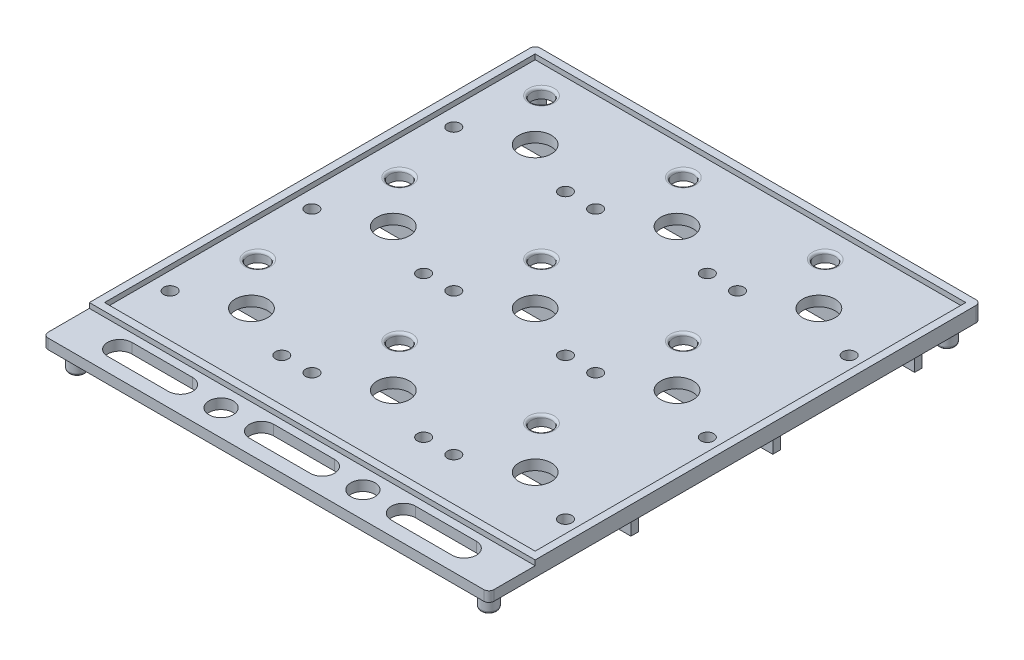
SolidWorks part; units mm, degrees
ref_plane "Front Plane" through (0, 0, 0) normal (0, 0, 1) x (1, 0, 0)
ref_plane "Top Plane" through (0, 0, 0) normal (0, 1, 0) x (1, 0, 0)
ref_plane "Right Plane" through (0, 0, 0) normal (1, 0, 0) x (0, 0, -1)
sketch "Sketch1" plane through (0, 0, 0) normal (0, 1, 0) x (1, 0, 0)
  line L1 (-25.4006, 105.41) -> (114.2994, 105.41)
  line L2 (-25.4006, 105.41) -> (-25.4006, -48.7985)
  line L3 (-25.4006, -48.7985) -> (114.2994, -48.7985)
  line L4 (114.2994, 105.41) -> (114.2994, -48.7985)
  circle A0 centre (44.45, 80.01) radius 5.08
  circle A1 centre (44.45, 80.01) radius 2.1
  circle A2 centre (61.95, 72.01) radius 2
  circle A3 centre (26.95, 72.01) radius 2
  circle A4 centre (0, 80.01) radius 5.08
  circle A5 centre (0, 80.01) radius 2.1
  circle A6 centre (17.5, 72.01) radius 2
  circle A7 centre (-17.5, 72.01) radius 2
  circle A8 centre (44.45, 35.56) radius 5.08
  circle A9 centre (44.45, 35.56) radius 2.1
  circle A10 centre (61.95, 27.56) radius 2
  circle A11 centre (26.95, 27.56) radius 2
  circle A12 centre (0, 35.56) radius 5.08
  circle A13 centre (0, 35.56) radius 2.1
  circle A14 centre (17.5, 27.56) radius 2
  circle A15 centre (-17.5, 27.56) radius 2
  circle A16 centre (44.45, -8.89) radius 5.08
  circle A17 centre (44.45, -8.89) radius 2.1
  circle A18 centre (61.95, -16.89) radius 2
  circle A19 centre (26.95, -16.89) radius 2
  circle A20 centre (0, -8.89) radius 5.08
  circle A21 centre (0, -8.89) radius 2.1
  circle A22 centre (17.5, -16.89) radius 2
  circle A23 centre (-17.5, -16.89) radius 2
  circle A24 centre (88.9, 80.01) radius 5.08
  circle A25 centre (88.9, 80.01) radius 2.1
  circle A26 centre (106.4, 72.01) radius 2
  circle A27 centre (71.4, 72.01) radius 2
  circle A28 centre (88.9, 35.56) radius 5.08
  circle A29 centre (88.9, 35.56) radius 2.1
  circle A30 centre (106.4, 27.56) radius 2
  circle A31 centre (71.4, 27.56) radius 2
  circle A32 centre (88.9, -8.89) radius 5.08
  circle A33 centre (88.9, -8.89) radius 2.1
  circle A34 centre (106.4, -16.89) radius 2
  circle A35 centre (71.4, -16.89) radius 2
  dimension "D3" = 7.8994
  dimension "D4" = 4
  dimension "D5" = 35
  dimension "D6" = 8
  dimension "D1" = 10.16
  dimension "D2" = 4
  dimension "D13" = 17.5
  dimension "D7" = 25.4
  dimension "D8" = 0
  dimension "D9" = 154.2085
  dimension "D10" = 139.7
  dimension "D11" = 3
  dimension "D12" = 3
extrude "Boss-Extrude4" add sketch "Sketch1" along normal blind 3.175 contours L4 L1 L2 L3 A27 A26 A24 region at (44.4494, 0, -28.0568)
sketch "Sketch4" plane through (0, 3.175, 0) normal (0, 1, 0) x (1, 0, 0)
  line L0 (-25.4006, 105.41) -> (-25.4006, -48.7985) construction
  line L1 (-25.4006, -31.9087) -> (114.2994, -31.9087)
  line L2 (-25.4006, -31.9087) -> (-25.4006, -34.29)
  line L3 (-25.4006, -34.29) -> (114.2994, -34.29)
  line L4 (114.2994, -31.9087) -> (114.2994, -34.29)
  line L5 (114.2994, 105.41) -> (114.2994, -48.7985) construction
  line L7 (-25.4006, -48.7985) -> (114.2994, -48.7985) construction
  dimension "D1" = 16.8897
  dimension "D2" = 14.5085
extrude "Boss-Extrude7" add sketch "Sketch4" along normal blind 1.5875
sketch "Sketch5" plane through (0, 3.175, 0) normal (0, -1, 0) x (1, 0, 0)
  line L0 (-25.4006, -105.41) -> (114.2994, -105.41) construction
  line L1 (-25.4006, -105.41) -> (-25.4006, 31.9087) construction
  circle A0 centre (-12.3037, -94.3) radius 3.175
  circle A1 centre (32.1463, -94.3) radius 3.175
  circle A2 centre (76.5963, -94.3) radius 3.175
  circle A3 centre (32.1463, -49.85) radius 3.175
  circle A4 centre (76.5963, -49.85) radius 3.175
  circle A5 centre (32.1463, -5.4) radius 3.175
  circle A6 centre (76.5963, -5.4) radius 3.175
  circle A7 centre (-12.3037, -49.85) radius 3.175
  circle A8 centre (-12.3037, -5.4) radius 3.175
  dimension "D1" = 11.11
  dimension "D2" = 13.0969
  dimension "D3" = 3
  dimension "D5" = 6.35
  dimension "D4" = 3
extrude "Cut-Extrude1" cut sketch "Sketch5" along normal up to next contours A0 | A1 | A2 | A4 | A3 | A7 | A8 | A5 | A6 region at (-12.3037, 3.175, -94.3) region at (32.1463, 3.175, -94.3) region at (76.5963, 3.175, -94.3) region at (32.1463, 3.175, -49.85) region at (76.5963, 3.175, -49.85) region at (32.1463, 3.175, -5.4) region at (76.5963, 3.175, -5.4) region at (-12.3037, 3.175, -49.85) region at (-12.3037, 3.175, -5.4)
sketch "Sketch7" plane through (0, 3.175, 0) normal (0, 1, 0) x (1, 0, 0)
  line L0 (9.525, -40.64) -> (-9.525, -40.64) construction
  line L1 (9.525, -44.4349) -> (-9.525, -44.4349)
  line L2 (9.525, -36.8451) -> (-9.525, -36.8451)
  line L3 (53.975, -40.64) -> (34.925, -40.64) construction
  line L4 (53.975, -44.4349) -> (34.925, -44.4349)
  line L5 (53.975, -36.8451) -> (34.925, -36.8451)
  line L6 (98.425, -40.64) -> (79.375, -40.64) construction
  line L7 (98.425, -44.4349) -> (79.375, -44.4349)
  line L8 (98.425, -36.8451) -> (79.375, -36.8451)
  line L9 (-25.4006, -34.29) -> (114.2994, -34.29) construction
  line L10 (-25.4006, -34.29) -> (114.2994, -34.29) construction
  arc A0 (9.525, -44.4349) -> (9.525, -36.8451) centre (9.525, -40.64) ccw
  arc A1 (-9.525, -36.8451) -> (-9.525, -44.4349) centre (-9.525, -40.64) ccw
  arc A2 (53.975, -44.4349) -> (53.975, -36.8451) centre (53.975, -40.64) ccw
  arc A3 (34.925, -36.8451) -> (34.925, -44.4349) centre (34.925, -40.64) ccw
  arc A4 (98.425, -44.4349) -> (98.425, -36.8451) centre (98.425, -40.64) ccw
  arc A5 (79.375, -36.8451) -> (79.375, -44.4349) centre (79.375, -40.64) ccw
  circle A6 centre (22.225, -40.64) radius 3.7949
  circle A8 centre (66.675, -40.64) radius 3.7949
  point P2 (0, -40.64)
  point P11 (44.45, -40.64)
  point P18 (88.9, -40.64)
  dimension "D4" = 12.7
  dimension "D1" = 0
  dimension "D2" = 19.05
  dimension "D6" = 12.7
  dimension "D8" = 6.35
  dimension "D10" = 6.35
  dimension "D11" = 6.35
  dimension "D3" = 3
extrude "Cut-Extrude2" cut sketch "Sketch7" against normal up to next
fillet "Fillet1" radius 0.7937 9 edges at (-12.3037, 3.175, -46.675) (32.1463, 3.175, -46.675) (76.5963, 3.175, -46.675) (76.5963, 3.175, -91.125) (32.1463, 3.175, -91.125) (-12.3037, 3.175, -91.125) (76.5963, 3.175, -2.225) (32.1463, 3.175, -2.225) (-12.3037, 3.175, -2.225)
sketch "Sketch8" plane through (0, 0, 0) normal (0, 1, 0) x (1, 0, 0)
  line L0 (-25.4006, 105.41) -> (-25.4006, -48.7985) construction
  line L1 (-25.4006, 0.6375) -> (114.2994, 0.6375)
  line L2 (-25.4006, 0.6375) -> (-25.4006, -1.7437)
  line L3 (-25.4006, -1.7437) -> (114.2994, -1.7437)
  line L4 (114.2994, 0.6375) -> (114.2994, -1.7437)
  line L5 (114.2994, 105.41) -> (114.2994, -31.9087) construction
  circle A0 centre (-12.3037, 5.4) radius 3.175 construction
  dimension "D1" = 4.7625
  dimension "D2" = 2.3813
extrude "Boss-Extrude8" add sketch "Sketch8" against normal blind 6.35
pattern_linear "LPattern2" count 3 spacing 44.45 along (0, 0, -1) of "Boss-Extrude8"
sketch "Sketch9" plane through (0, 0, 0) normal (0, -1, 0) x (1, 0, 0)
  line L1 (-25.4006, 48.7985) -> (114.2994, 48.7985)
  line L2 (-25.4006, 48.7985) -> (-25.4006, -105.41)
  line L3 (-25.4006, -105.41) -> (114.2994, -105.41)
  line L4 (114.2994, 48.7985) -> (114.2994, -105.41)
  line L5 (111.7594, -102.87) -> (-22.8606, -102.87)
  line L6 (111.7594, -102.87) -> (111.7594, 46.2585)
  line L7 (111.7594, 46.2585) -> (-22.8606, 46.2585)
  line L8 (-22.8606, -102.87) -> (-22.8606, 46.2585)
  dimension "D1" = 2.54
  dimension "D2" = 2.54
  dimension "D3" = 2.54
  dimension "D4" = 2.54
extrude "Cut-Extrude3" cut sketch "Sketch9" along normal blind 6.35
sketch "Sketch10" plane through (0, 3.175, 0) normal (0, 1, 0) x (1, 0, 0)
  line L0 (114.2994, -31.9087) -> (-25.4006, -31.9087) construction
  line L1 (-25.4006, -34.29) -> (114.2994, -34.29)
  line L2 (-25.4006, -34.29) -> (-25.4006, 105.41)
  line L3 (-25.4006, 105.41) -> (114.2994, 105.41)
  line L4 (114.2994, -34.29) -> (114.2994, 105.41)
  line L5 (111.9181, -31.9087) -> (-23.0194, -31.9087)
  line L6 (111.9181, -31.9087) -> (111.9181, 103.0288)
  line L7 (111.9181, 103.0288) -> (-23.0194, 103.0288)
  line L8 (-23.0194, -31.9087) -> (-23.0194, 103.0288)
  line L9 (-25.4006, 105.41) -> (-25.4006, -31.9087) construction
  dimension "D1" = 2.3813
  dimension "D2" = 2.3813
  dimension "D3" = 2.3813
  dimension "D4" = 2.3813
extrude "Boss-Extrude9" add sketch "Sketch10" along normal blind 1.5875
sketch "Sketch11" plane through (0, 0, 0) normal (0, -1, 0) x (1, 0, 0)
  line L0 (-25.4006, -105.41) -> (114.2994, -105.41) construction
  line L1 (-25.4006, -105.41) -> (-25.4006, 48.7985) construction
  line L2 (114.2994, -105.41) -> (114.2994, 48.7985) construction
  line L3 (-25.4006, 48.7985) -> (114.2994, 48.7985) construction
  circle A0 centre (-20.0666, 43.4645) radius 2.54
  circle A1 centre (108.9654, 43.4645) radius 2.54
  circle A2 centre (108.9654, -100.076) radius 2.54
  circle A3 centre (-20.0666, -100.076) radius 2.54
  dimension "D2" = 5.08
  dimension "D3" = 5.334
  dimension "D4" = 5.334
  dimension "D5" = 5.334
  dimension "D6" = 5.08
  dimension "D7" = 5.334
  dimension "D8" = 5.08
  dimension "D9" = 5.334
  dimension "D10" = 5.334
  dimension "D11" = 5.334
  dimension "D12" = 5.08
  dimension "D1" = 5.334
extrude "Boss-Extrude10" add sketch "Sketch11" along normal blind 6.35
fillet "Fillet5" radius 0.7937 10 edges at (-20.0666, -6.35, -102.616) (108.9654, -6.35, -102.616) (44.4494, 0, -87.1563) (44.4494, 0, -42.7063) (44.4494, 0, -89.5375) (44.4494, 0, -45.0875) (44.4494, 0, -0.6375) (44.4494, 0, 1.7437) (108.9654, -6.35, 40.9245) (-20.0666, -6.35, 40.9245)
fillet "Fillet6" radius 1.5875 4 edges at (-25.4006, 1.5875, 48.7985) (114.2994, 1.5875, 48.7985) (114.2994, 2.3812, -105.41) (-25.4006, 2.3812, -105.41)
